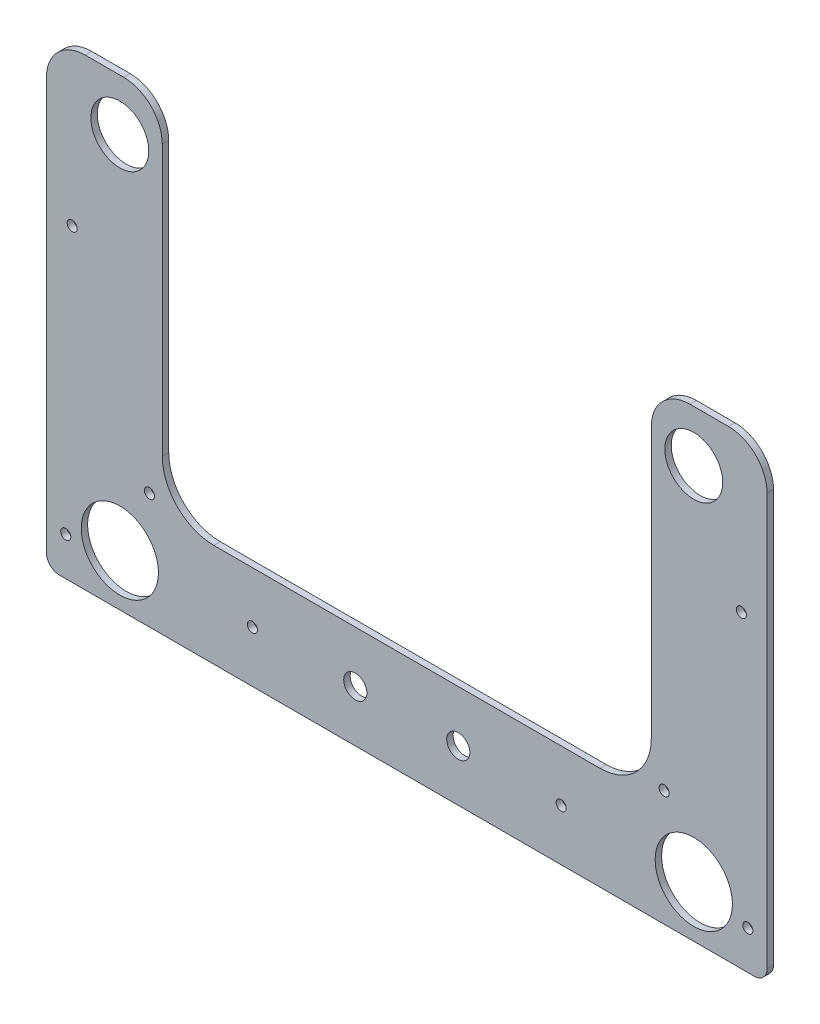
SolidWorks part; units mm, degrees
material "6061 Alloy"
ref_plane "Front Plane" through (0, 0, 0) normal (0, 0, 1) x (1, 0, 0)
ref_plane "Top Plane" through (0, 0, 0) normal (0, 1, 0) x (1, 0, 0)
ref_plane "Right Plane" through (0, 0, 0) normal (1, 0, 0) x (0, 0, -1)
sketch "Sketch1" plane through (0, 0, 0) normal (0, 0, 1) x (1, 0, 0)
  line L5 (120.65, -152.4) -> (120.65, -6.35)
  line L6 (127, 0) -> (171.45, 0) construction
  line L7 (177.8, -6.35) -> (177.8, -222.25)
  line L10 (0, -206.2199) -> (0, -63.6275) construction
  line L11 (-54.9244, 0) -> (300.6756, 0) construction
  line L13 (12.7, -177.8) -> (95.25, -177.8)
  line L14 (12.7, -228.6) -> (171.45, -228.6)
  line L15 (141.605, -25.4) -> (141.605, -84.2822) construction
  line L16 (141.605, -25.4) -> (141.605, -127) construction
  line L19 (-141.605, -19.05) -> (-141.605, -77.9322) construction
  line L20 (141.605, -25.4) -> (141.605, -203.2) construction
  line L22 (-120.65, -152.4) -> (-120.65, -6.35)
  line L23 (-12.7, -177.8) -> (-95.25, -177.8)
  line L24 (-12.7, -228.6) -> (-171.45, -228.6)
  line L25 (-177.8, -6.35) -> (-177.8, -222.25)
  line L26 (-12.7, -177.8) -> (12.7, -177.8)
  line L27 (-12.7, -228.6) -> (12.7, -228.6)
  line L28 (-177.8, -6.35) -> (-177.8, 6.35)
  line L29 (-165.1, 19.05) -> (-133.35, 19.05)
  line L30 (-120.65, 6.35) -> (-120.65, -6.35)
  line L31 (120.65, 6.35) -> (120.65, -6.35)
  line L32 (177.8, -6.35) -> (177.8, 6.35)
  line L33 (165.1, 19.05) -> (133.35, 19.05)
  arc A0 (95.25, -177.8) -> (120.65, -152.4) centre (95.25, -152.4) ccw
  arc A4 (120.65, -6.35) -> (127, 0) centre (127, -6.35) cw construction
  circle A8 centre (141.605, -25.4) radius 14.2875
  circle A9 centre (141.605, -25.4) radius 38.1 construction
  arc A10 (177.8, -6.35) -> (171.45, 0) centre (171.45, -6.35) ccw construction
  arc A11 (171.45, -228.6) -> (177.8, -222.25) centre (171.45, -222.25) ccw
  arc A14 (141.605, -82.55) -> (120.9214, -78.6758) centre (141.605, -25.4) ccw construction
  arc A15 (-141.605, -82.55) -> (-120.9214, -78.6758) centre (-141.605, -25.4) cw construction
  circle A16 centre (-141.605, -25.4) radius 38.1 construction
  circle A17 centre (-141.605, -25.4) radius 14.2875
  arc A19 (-95.25, -177.8) -> (-120.65, -152.4) centre (-95.25, -152.4) cw
  circle A20 centre (141.605, -127) radius 38.1 construction
  circle A21 centre (-141.605, -127) radius 38.1 construction
  arc A23 (-171.45, -228.6) -> (-177.8, -222.25) centre (-171.45, -222.25) cw
  circle A24 centre (-141.605, -203.2) radius 19.05
  circle A37 centre (141.605, -203.2) radius 19.05
  circle A39 centre (-76.2, -203.2) radius 2.4892
  circle A40 centre (76.2, -203.2) radius 2.4892
  circle A42 centre (-25.4, -203.2) radius 5.715
  arc A44 (-133.35, 19.05) -> (-120.65, 6.35) centre (-133.35, 6.35) cw
  arc A45 (-177.8, 6.35) -> (-165.1, 19.05) centre (-165.1, 6.35) cw
  arc A46 (133.35, 19.05) -> (120.65, 6.35) centre (133.35, 6.35) ccw
  arc A47 (177.8, 6.35) -> (165.1, 19.05) centre (165.1, 6.35) ccw
  circle A50 centre (-149.225, 6.35) radius 2.4892
  circle A53 centre (149.225, 6.35) radius 2.4892
  circle A54 centre (-168.275, -209.55) radius 2.4892
  circle A56 centre (168.275, -209.55) radius 2.4892
  circle A58 centre (-165.1, -76.2) radius 2.4892
  circle A59 centre (165.1, -76.2) radius 2.4892
  circle A60 centre (-127, -171.45) radius 2.4892
  circle A61 centre (127, -171.45) radius 2.4892
  circle A62 centre (25.4, -203.2) radius 5.715
  point P2 (177.8, -44.45)
  point P18 (177.8, 0)
  point P23 (177.8, -228.6)
  point P24 (177.8, -228.6)
  point P25 (120.65, -79.375)
  point P31 (177.8, 0)
  point P48 (-177.8, 0)
  point P49 (-177.8, -228.6)
  point P51 (-177.8, -44.45)
  point P78 (-141.605, -203.2)
  dimension "D6" = 25.4
  dimension "D7" = 6.35
  dimension "D8" = 6.35
  dimension "D9" = 177.8
  dimension "D10" = 28.575
  dimension "D12" = 76.2
  dimension "D13" = 57.15
  dimension "D15" = 38.1
  dimension "D18" = 76.2
  dimension "D21" = 4.9784
  dimension "D29" = 9.525
  dimension "D32" = 4.9784
  dimension "D35" = 11.43
  dimension "D40" = 12.7
  dimension "D43" = 4.9784
  dimension "D45" = 12.7
  dimension "D30" = 4.9784
  dimension "D41" = 4.9784
  dimension "D22" = 6.35
  dimension "D2" = 120.65
  dimension "D3" = 177.8
  dimension "D4" = 228.6
  dimension "D5" = 177.8
  dimension "D11" = 20.955
  dimension "`" = 25.4
  dimension "D14" = 57.15
  dimension "D16" = 184.15
  dimension "D17" = 101.6
  dimension "D19" = 25.4
  dimension "D20" = 101.6
  dimension "D23" = 57.15
  dimension "D25" = 25.4
  dimension "D26" = 19.05
  dimension "D27" = 25.4
  dimension "D28" = 25.4
  dimension "D31" = 25.4
  dimension "D33" = 12.7
  dimension "D34" = 25.4
  dimension "D39" = 19.05
  dimension "D44" = 28.575
  dimension "D24" = 95.25
extrude "Boss-Extrude3" add sketch "Sketch1" along normal blind 3.175
sketch "Sketch2" plane through (0, 0, 3.175) normal (0, 0, 1) x (1, 0, 0)
  line L0 (177.8, -222.25) -> (177.8, 6.35) construction
  line L1 (-177.8, 19.05) -> (177.8, 19.05)
  line L2 (-177.8, 19.05) -> (-177.8, 0)
  line L3 (-177.8, 0) -> (177.8, 0)
  line L4 (177.8, 19.05) -> (177.8, 0)
  line L5 (-177.8, 6.35) -> (-177.8, -222.25) construction
  line L7 (-133.35, 19.05) -> (-165.1, 19.05) construction
  dimension "D1" = 19.05
extrude "Cut-Extrude1" cut sketch "Sketch2" against normal through all
fillet "Fillet1" radius 19.05 4 edges at (177.8, 0, 1.5875) (120.65, 0, 1.5875) (-120.65, 0, 1.5875) (-177.8, 0, 1.5875)
